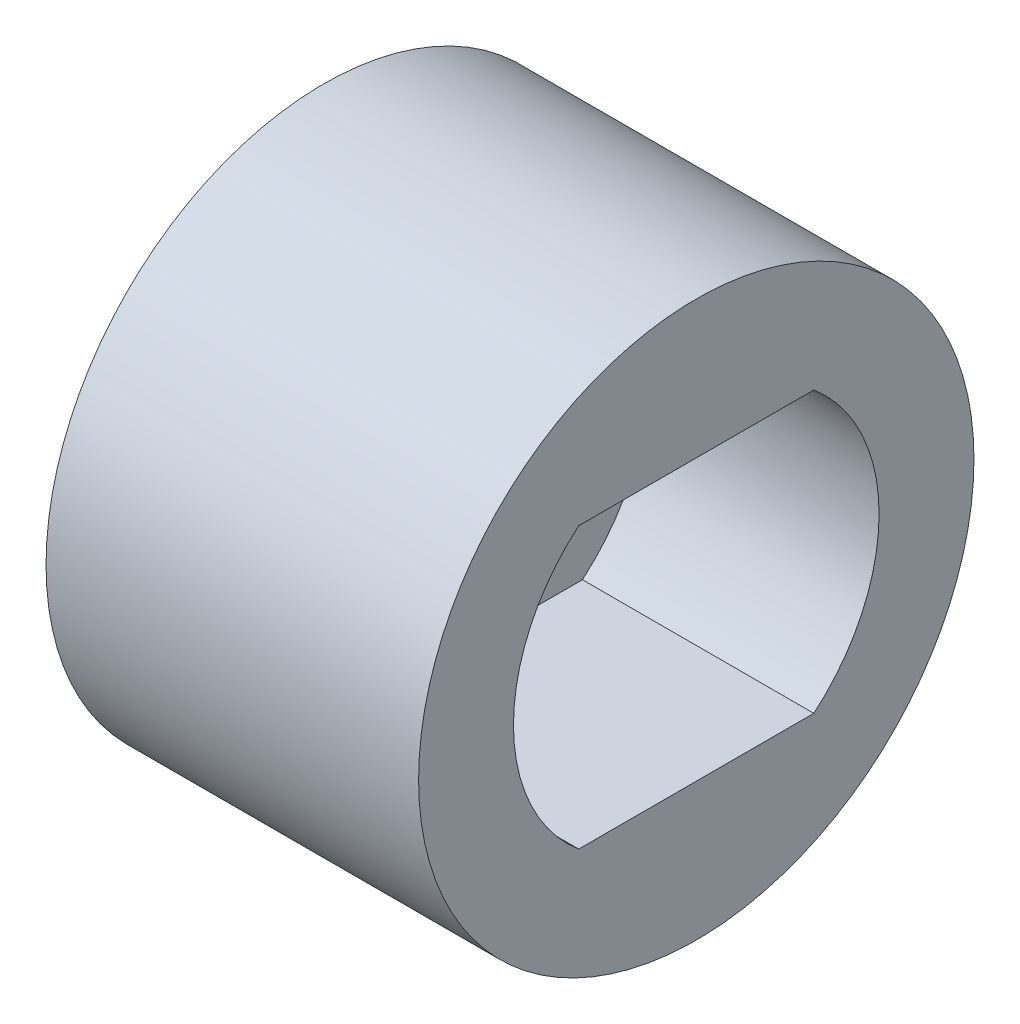
SolidWorks part; units mm, degrees
ref_plane "Plane1" through (0, 0, 0) normal (0, 0, 1) x (1, 0, 0)
ref_plane "Plane2" through (0, 0, 0) normal (0, 1, 0) x (1, 0, 0)
ref_plane "Plane3" through (0, 0, 0) normal (1, 0, 0) x (0, 0, -1)
other "Configuration Table"
sketch "HoldingSke" plane through (0, 0, 0) normal (0, 1, 0) x (1, 0, 0)
  line L0 (0, 0) -> (1.4863, -1.3383)
  line L1 (-15, 0) -> (100, 0) construction
  line L2 (0, 0) -> (-2.1039, 2.3779)
  line L3 (0, 0) -> (-11.863, 4.5341)
  line L4 (0, 0) -> (6.4178, 5.7786)
  line L5 (0, 0) -> (-23.7986, -8.8762)
  line L6 (0, 0) -> (-10.5278, -7.1032)
  line L7 (-2.1039, 2.3779) -> (3.3635, 27.1825)
  line L8 (-76.2, 2.8779) -> (-54.61, 2.8779)
  line L9 (-71.009, 38.7566) -> (-53.1078, 45.2721)
  line L10 (-76.2, 71.12) -> (104.1128, 71.12)
  line L11 (0, 0) -> (-5.1, 0)
  line L12 (-76.2, 101.6) -> (-76.181, 101.6)
  line L13 (24.9733, 27.94) -> (52.9518, 28.4284)
  line L14 (24.9733, 27.94) -> (24.9743, 27.94)
  line L15 (24.9733, 27.94) -> (100.4006, 29.5858)
  circle A0 centre (0, 0) radius 12
  circle A1 centre (0, 0) radius 12.7
  circle A2 centre (0, 0) radius 12.7
  dimension "Num_teeth" = 42
  dimension "Pitch_radius" = 180.3128
  dimension "Width" = 5.1
  dimension "Diameter" = 24
sketch "BasProSke" plane through (0, 0, 0) normal (0, 1, 0) x (1, 0, 0)
  line L0 (-10, 0) -> (60, 0) construction
  line L1 (0, 10) -> (0, 12)
  line L2 (0, 10) -> (5.1, 10)
  line L3 (5.1, 10) -> (5.1, 12)
  line L4 (5.1, 12) -> (0, 12)
  dimension "Thickness" = 5.1
  dimension "Diameter" = 24
revolve "Base-Revolve" add sketch "BasProSke" angle 360 about L0
sketch "TooCutSke" plane through (0, 0, 0) normal (1, 0, 0) x (0, 0, -1)
  line L3 (0.4401, 10.4908) -> (0.4401, 53.6633) construction
  line L4 (0, 0) -> (0, 59.563) construction
  line L5 (0, 0) -> (-5.1061, 68.1364) construction
  line L6 (-4.4466, 8.5718) -> (37.0734, 11.6833) construction
  circle A0 centre (0, 0) radius 10.5 construction
  circle A1 centre (0, 0) radius 11.126 construction
  circle A2 centre (0, 0) radius 8.8801 construction
  circle A3 centre (0, 0) radius 9.9746 construction
  arc A4 (0.6178, 9.9555) -> (0.1407, 11.1251) centre (-4.4466, 8.5718) ccw
  arc A5 (0.6178, 9.9555) -> (-0.6178, 9.9555) centre (0, 0) ccw
  arc A6 (0.1407, 11.1251) -> (-0.1407, 11.1251) centre (0, 0) ccw
  arc A7 (-0.1407, 11.1251) -> (-0.6178, 9.9555) centre (4.4466, 8.5718) ccw
extrude "ToothCut" cut sketch "TooCutSke" along normal through all
fillet "Breaks" [suppressed] radius 0.05
fillet "RootFillets" [suppressed] radius 0.126
pattern_circular "TeethCuts" count 42 every 8.571 about axis through (-10, 0, 0) along (1, 0, 0) of "RootFillets", "Breaks", "ToothCut"
sketch "草图1" plane through (5.1, 0, 0) normal (1, 0, 0) x (0, 0, -1)
  line L1 (-7.9, -6.05) -> (7.9, -6.05)
  line L2 (-7.9, -6.05) -> (-7.9, 6.05)
  line L3 (-7.9, 6.05) -> (7.9, 6.05)
  line L4 (7.9, -6.05) -> (7.9, 6.05)
  line L5 (-7.9, -6.05) -> (7.9, 6.05) construction
  line L6 (-7.9, 6.05) -> (7.9, -6.05) construction
  circle A0 centre (0, 0) radius 12
  circle A1 centre (0, 0) radius 7.9
  circle A2 centre (0, 0) radius 2.5
  dimension "D1" = 5
  dimension "D2" = 12.1
  dimension "D4" = 24
  dimension "D3" = 15.8
extrude "凸台-拉伸1" add sketch "草图1" along normal blind 11 contours A0 | A2
extrude "切除-拉伸1" cut sketch "草图1<3>" along normal up to next from offset 1 contours L3 A1 L1 A2 region at (5.1, -3.2534, 6.98)
sketch "草图1<3>" plane through (5.1, 0, 0) normal (1, 0, 0) x (0, 0, -1) same geometry as "草图1"
equation "' \"Module@HoldingSke\" = 6.35"
equation "' \"Num_teeth@HoldingSke\" = 24"
equation "' \"Ap@HoldingSke\" =  14.5"
equation "' \"Ap@HoldingSke\" = 14.5"
equation "' \"Width@HoldingSke\" = 12"
equation "' \"Diameter@HoldingSke\" = 8 * 25.4"
equation "' \"Show_teeth@HoldingSke\" = 100"
equation "' \"Backlash@HoldingSke\" = 0.009 * 25.4"
equation "' \"Addendum_fac@HoldingSke\" = 1.0"
equation "' \"Dedendum_fac@HoldingSke\" = 1.25"
equation "' \"Dedendum_add@HoldingSke\" = 0.00005 * 25.4"
equation "' \"Clearance_fac@HoldingSke\" = 0.25"
equation "\"Pitch@HoldingSke\" = 1 / \"Module@HoldingSke\" "
equation "\"Overcut_dia@TooCutSke\" = (\"Num_teeth@HoldingSke\" - 2 * \"Addendum_fac@HoldingSke\") / \"Pitch@HoldingSke\" - 0.002 * 25.4"
equation "\"Pitch_dia@TooCutSke\" = \"Num_teeth@HoldingSke\" / \"Pitch@HoldingSke\""
equation "\"Base_dia@TooCutSke\" = \"Num_teeth@HoldingSke\" / \"Pitch@HoldingSke\" * cos((\"Ap@HoldingSke\"  * 3.14159265 / 180)) * 0.90"
equation "\"Root_dia@TooCutSke\" = \"Num_teeth@HoldingSke\"  / \"Pitch@HoldingSke\" + 2 *  \"Dedendum_fac@HoldingSke\"/ \"Pitch@HoldingSke\" + \"Dedendum_add@HoldingSke\" * 2"
equation "\"Half_ang@TooCutSke\" = 180 / \"Num_teeth@HoldingSke\""
equation "\"Half_CT@TooCutSke\" = \"Num_teeth@HoldingSke\" / \"Pitch@HoldingSke\" * sin((3.14159265 / 2 / \"Num_teeth@HoldingSke\")) / 2 + 10 * \"Backlash@HoldingSke\" / 4"
equation "\"Flank_rad@TooCutSke\" = \"Num_teeth@HoldingSke\" / \"Pitch@HoldingSke\" / 4"
equation "\"Radius@RootFillets\"= \"Clearance_fac@HoldingSke\" / \"Pitch@HoldingSke\" + \"Dedendum_add@HoldingSke\""
equation "\"Break_rad@Breaks\" = 0.02 / \"Pitch@HoldingSke\" * 5"
equation "\"Num_teeth@TeethCuts\" = int( \"Show_teeth@HoldingSke\" ) + 1"
equation "\"Num_teeth@TeethCuts\" = ((sgn( \"Num_teeth@TeethCuts\" - \"Num_teeth@HoldingSke\" )-1)*( \"Num_teeth@TeethCuts\" - \"Num_teeth@HoldingSke\" ))/-2+ \"Num_teeth@HoldingSke\""
equation "\"Num_teeth@TeethCuts\" = ((sgn( \"Num_teeth@TeethCuts\" - 2.0)+1)*( \"Num_teeth@TeethCuts\" - 2.0))/2 +2.0"
equation "\"Angle@TeethCuts\" = 360.0 / \"Num_teeth@HoldingSke\""
equation "\"Diameter@BasProSke\" = \"Num_teeth@HoldingSke\"  / \"Pitch@HoldingSke\" + 2 *  \"Dedendum_fac@HoldingSke\"/ \"Pitch@HoldingSke\" + \"Dedendum_add@HoldingSke\" * 2 + 0.002 * 25.4"
equation "\"Diameter@BasProSke\" = ((sgn( \"Diameter@BasProSke\"  - \"Diameter@HoldingSke\" )+1)*( \"Diameter@BasProSke\"  - \"Diameter@HoldingSke\" ))/2 + \"Diameter@HoldingSke\""
equation "\"Inside_diameter@BasProSke\" =  (\"Num_teeth@HoldingSke\" - 2 * \"Addendum_fac@HoldingSke\") / \"Pitch@HoldingSke\" "
equation "\"Thickness@BasProSke\"  = \"Width@HoldingSke\""
